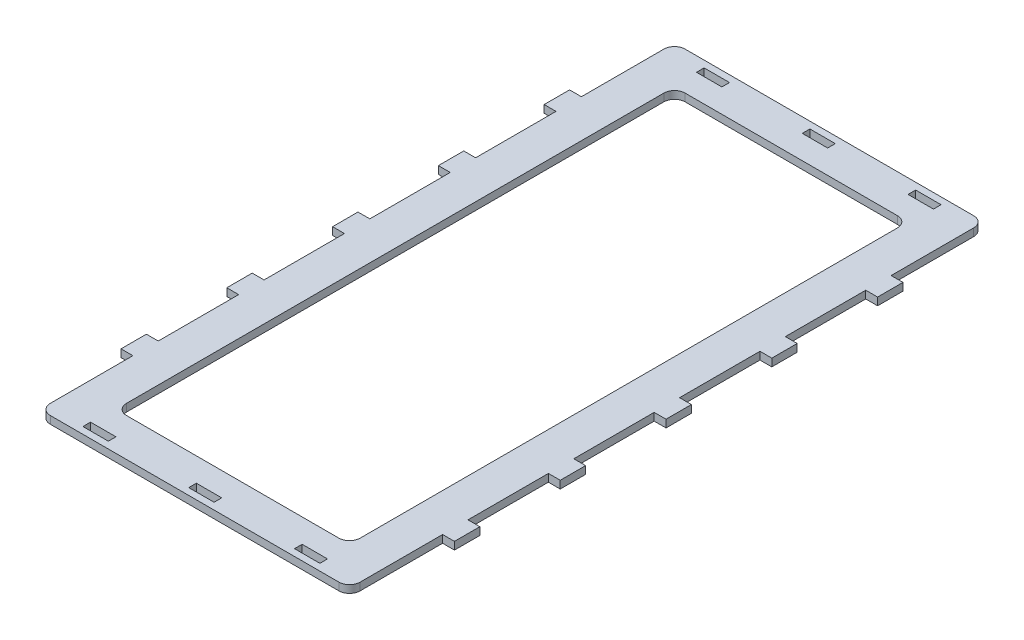
SolidWorks part; units mm, degrees
ref_plane "前视基准面" through (0, 0, 0) normal (0, 0, 1) x (1, 0, 0)
ref_plane "上视基准面" through (0, 0, 0) normal (0, 1, 0) x (1, 0, 0)
ref_plane "右视基准面" through (0, 0, 0) normal (1, 0, 0) x (0, 0, -1)
other "Configuration Table"
sketch "草图1" plane through (0, 0, 0) normal (0, 1, 0) x (1, 0, 0)
  line L1 (-366, 750) -> (366, 750)
  line L2 (-366, 750) -> (-366, -750)
  line L3 (-366, -750) -> (366, -750)
  line L4 (366, 750) -> (366, -750)
  line L5 (-394, -470) -> (-366, -470)
  line L6 (-394, -470) -> (-394, -530)
  line L7 (-394, -530) -> (-366, -530)
  line L8 (-366, -470) -> (-366, -530)
  line L9 (-280, -734) -> (-220, -734)
  line L10 (-280, -734) -> (-280, -716)
  line L11 (-280, -716) -> (-220, -716)
  line L12 (-220, -734) -> (-220, -716)
  line L13 (-276, 660) -> (276, 660)
  line L14 (-276, 660) -> (-276, -660)
  line L15 (-276, -660) -> (276, -660)
  line L16 (276, 660) -> (276, -660)
  point P4 (-366, 0)
  point P6 (0, -750)
  point P11 (-394, -500)
  point P20 (0, -660)
  point P21 (-276, 0)
  point P22 (-250, -734)
  point P23 (-220, -725)
  dimension "D1" = 732
  dimension "D2" = 1500
  dimension "D3" = 250
  dimension "D4" = 28
  dimension "D5" = 60
  dimension "D6" = 90
  dimension "D7" = 90
  dimension "D8" = 60
  dimension "D9" = 18
  dimension "D10" = 116
  dimension "D11" = 25
extrude "凸台-拉伸1" add sketch "草图1" along normal blind 18 contours L2 L3 L4 L1 | L14 L15 L16 L13
extrude "凸台-拉伸2" add sketch "草图1<3>" along normal up to surface (18 mm away) contours L6 L7 L8 L5 up to face at (0, 18, 0)
sketch "草图1<3>" plane through (0, 0, 0) normal (0, 1, 0) x (1, 0, 0) same geometry as "草图1"
pattern_linear "阵列(线性)1" count 5 spacing 250 along (0, 0, -1) of "凸台-拉伸2"
mirror "镜向1" about plane through (0, 0, 0) normal (1, 0, 0) of "阵列(线性)1", "凸台-拉伸2"
extrude "切除-拉伸1" cut sketch "草图1<4>" along normal through all contours L12 L11 L10 L9
sketch "草图1<4>" plane through (0, 0, 0) normal (0, 1, 0) x (1, 0, 0) same geometry as "草图1"
pattern_linear "阵列(线性)2" count 3 spacing 250 along (1, 0, 0) of "切除-拉伸1"
mirror "镜向2" about plane through (0, 0, 0) normal (0, 0, 1) of "阵列(线性)2", "切除-拉伸1"
fillet "圆角1" radius 25 4 edges at (-366, 9, -750) (366, 9, -750) (366, 9, 750) (-366, 9, 750)
fillet "圆角2" radius 25 4 edges at (-276, 9, -660) (276, 9, -660) (276, 9, 660) (-276, 9, 660)
